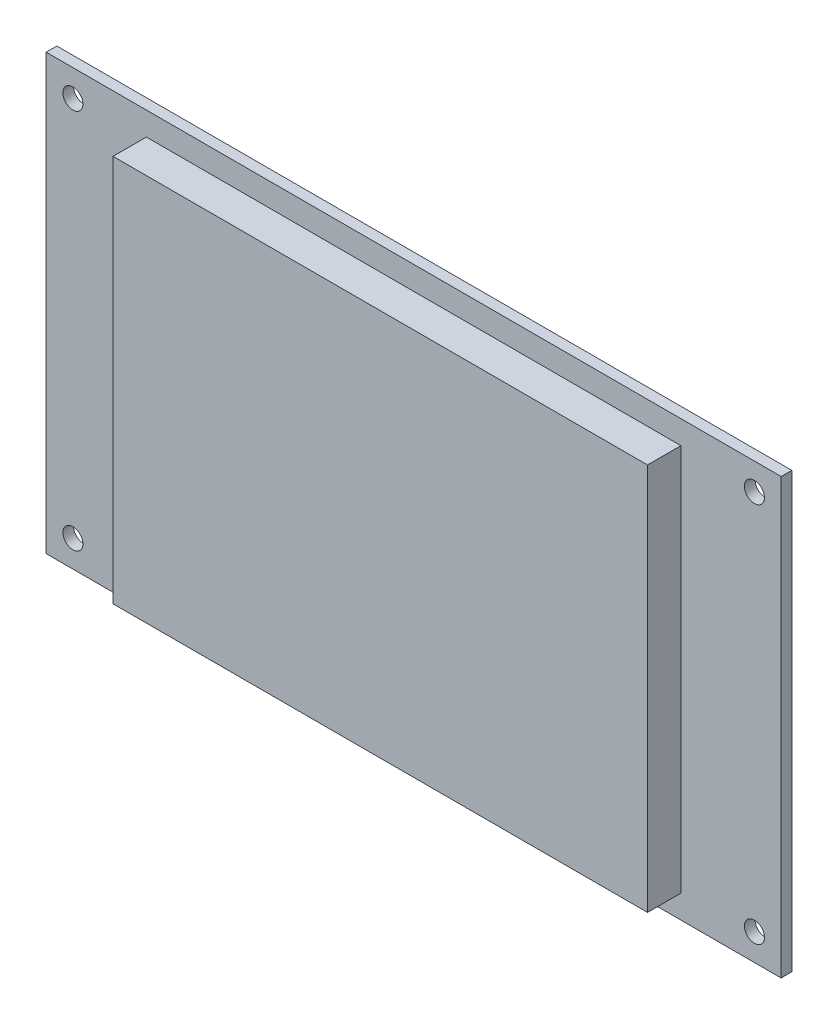
SolidWorks part; units mm, degrees
ref_plane "Front Plane" through (0, 0, 0) normal (0, 0, 1) x (1, 0, 0)
ref_plane "Top Plane" through (0, 0, 0) normal (0, 1, 0) x (1, 0, 0)
ref_plane "Right Plane" through (0, 0, 0) normal (1, 0, 0) x (0, 0, -1)
sketch "Sketch1" plane through (0, 0, 0) normal (0, 0, 1) x (1, 0, 0)
  line L1 (-55, -32.5) -> (55, -32.5)
  line L2 (-55, -32.5) -> (-55, 32.5)
  line L3 (-55, 32.5) -> (55, 32.5)
  line L4 (55, -32.5) -> (55, 32.5)
  line L5 (-55, -32.5) -> (55, 32.5) construction
  line L6 (-55, 32.5) -> (55, -32.5) construction
  line L7 (51, 28.5) -> (-51, 28.5) construction
  line L8 (51, 28.5) -> (51, -28.5) construction
  line L9 (51, -28.5) -> (-51, -28.5) construction
  line L10 (-51, 28.5) -> (-51, -28.5) construction
  line L11 (-40, 29) -> (40, 29)
  line L12 (-40, 29) -> (-40, -29)
  line L13 (-40, -29) -> (40, -29)
  line L14 (40, 29) -> (40, -29)
  circle A0 centre (-51, 28.5) radius 1.5
  circle A1 centre (51, 28.5) radius 1.5
  circle A2 centre (51, -28.5) radius 1.5
  circle A3 centre (-51, -28.5) radius 1.5
  point P0 (0, 0)
  point P14 (-51, 0)
  point P15 (0, 28.5)
  point P23 (-40, 0)
  dimension "D3" = 3
  dimension "D1" = 65
  dimension "D2" = 110
  dimension "D4" = 102
  dimension "D5" = 57
  dimension "D6" = 58
  dimension "D7" = 15
  dimension "D8" = 15
extrude "Boss-Extrude1" add sketch "Sketch1" against normal blind 1.6 contours L14 L11 L12 L13 | L1 L4 L3 L2 A3 A2 A1 A0 L11 L14 L13 L12 region at (-53.7223, 0, 0) region at (0, 0, 0)
extrude "Boss-Extrude2" add sketch "Sketch1<3>" along normal blind 5 contours L14 L11 L12 L13 region at (0, 0, 0)
sketch "Sketch1<3>" plane through (0, 0, 0) normal (0, 0, 1) x (1, 0, 0) same geometry as "Sketch1"
